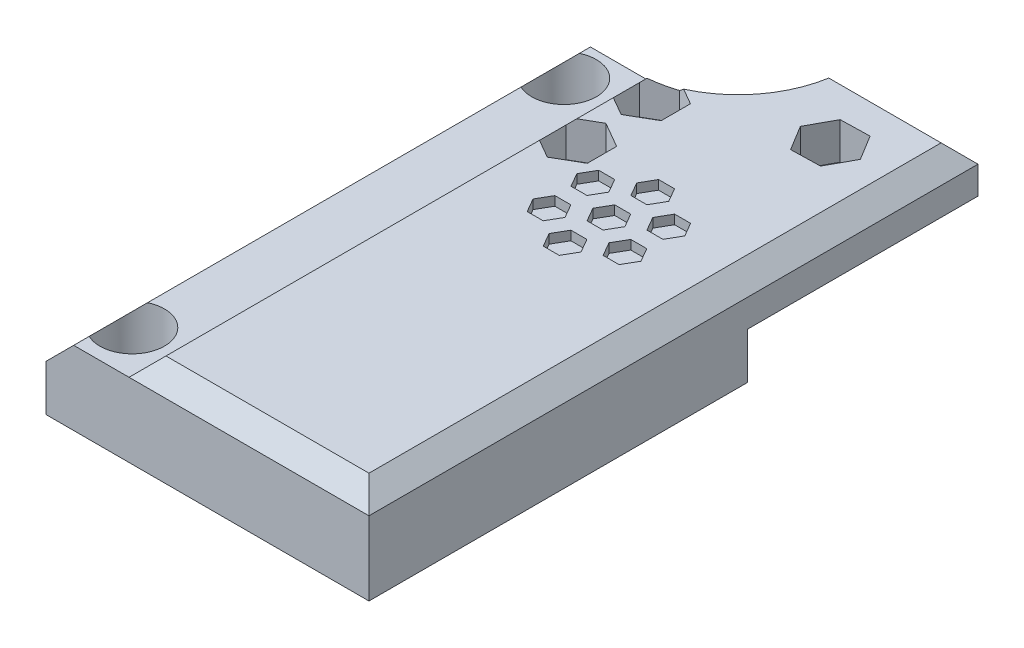
SolidWorks part; units mm, degrees
ref_plane "Front Plane" through (0, 0, 0) normal (0, 0, 1) x (1, 0, 0)
ref_plane "Top Plane" through (0, 0, 0) normal (0, 1, 0) x (1, 0, 0)
ref_plane "Right Plane" through (0, 0, 0) normal (1, 0, 0) x (0, 0, -1)
sketch "Sketch1" plane through (0, 0, 0) normal (0, 1, 0) x (1, 0, 0)
  line L1 (0, 0) -> (26, 0)
  line L2 (0, 0) -> (0, 41)
  line L3 (0, 41) -> (26, 41)
  line L4 (26, 0) -> (26, 41)
  dimension "D1" = 41
  dimension "D2" = 26
extrude "Boss-Extrude1" add sketch "Sketch1" along normal blind 10
sketch "Sketch2" plane through (0, 0, -41) normal (0, 0, -1) x (-1, 0, 0)
  line L0 (-26, 10) -> (-26, 0) construction
  line L1 (-26, 5) -> (0, 5)
  line L2 (-26, 5) -> (-26, 10)
  line L3 (-26, 10) -> (0, 10)
  line L4 (0, 5) -> (0, 10)
extrude "Boss-Extrude2" add sketch "Sketch2" along normal blind 25
sketch "Sketch3" plane through (0, 10, 0) normal (0, 1, 0) x (1, 0, 0)
  line L0 (0, 66) -> (0, 0) construction
  line L1 (0, 66) -> (26, 66) construction
  line L2 (0, 56) -> (0, 66)
  line L3 (0, 66) -> (10, 66)
  arc A0 (0, 56) -> (10, 66) centre (0, 66) ccw
  dimension "D1" = 10
extrude "Cut-Extrude1" cut sketch "Sketch3" against normal up to next
chamfer "Chamfer1" distance 2 angle 45 5 edges at (18, 10, -66) (7.0711, 10, -58.9289) (0, 10, -28) (26, 10, -33) (13, 10, 0)
sketch "Sketch4" plane through (0, 0, 0) normal (-1, 0, 0) x (0, 0, 1)
  line L1 (-56, 8) -> (0, 8)
  line L2 (-56, 8) -> (-56, 0)
  line L3 (-56, 0) -> (0, 0)
  line L4 (0, 8) -> (0, 0)
extrude "Boss-Extrude3" add sketch "Sketch4" along normal blind 9
sketch "Sketch5" plane through (0, 8, 0) normal (0, 1, 0) x (1, 0, 0)
  line L0 (-4.5, 51.6375) -> (-4.5, 4.8375) construction
  line L1 (-9, 0) -> (-9, 56) construction
  circle A0 centre (-4.5, 51.6375) radius 2.15
  circle A1 centre (-4.5, 4.8375) radius 2.15
  dimension "D1" = 4.3
  dimension "D2" = 4.5
  dimension "D3" = 46.8
extrude "Cut-Extrude2" cut sketch "Sketch5" against normal up to next
sketch "Sketch6" plane through (0, 8, 0) normal (0, 1, 0) x (1, 0, 0)
  circle A0 centre (-4.5, 51.6375) radius 3.5
  circle A1 centre (-4.5, 4.8375) radius 3.5
  dimension "D1" = 7
extrude "Cut-Extrude3" cut sketch "Sketch6" against normal blind 5
chamfer "Chamfer3" distance 3 angle 45 1 edges at (-9, 8, -28)
sketch "Sketch10" plane through (0, 10, 0) normal (0, 1, 0) x (1, 0, 0)
  line L0 (24, 2) -> (24, 64) construction
  line L1 (14.7321, 39) -> (13.866, 40.5)
  line L2 (13.866, 40.5) -> (12.134, 40.5)
  line L3 (12.134, 40.5) -> (11.2679, 39)
  line L4 (11.2679, 39) -> (12.134, 37.5)
  line L5 (12.134, 37.5) -> (13.866, 37.5)
  line L6 (13.866, 37.5) -> (14.7321, 39)
  line L7 (14.7321, 43.75) -> (13.866, 45.25)
  line L8 (13.866, 45.25) -> (12.134, 45.25)
  line L9 (12.134, 45.25) -> (11.2679, 43.75)
  line L10 (11.2679, 43.75) -> (12.134, 42.25)
  line L11 (12.134, 42.25) -> (13.866, 42.25)
  line L12 (13.866, 42.25) -> (14.7321, 43.75)
  line L13 (0, 0) -> (13, 39) construction
  line L14 (13, 39) -> (13, 0) construction
  line L16 (13, 0) -> (0, 0) construction
  line L17 (0, 0) -> (13, 0) construction
  line L19 (2, 2) -> (24, 2) construction
  line L20 (17.9796, 39.875) -> (18.8457, 41.375)
  line L21 (18.8457, 41.375) -> (17.9796, 42.875)
  line L22 (17.9796, 42.875) -> (16.2476, 42.875)
  line L23 (16.2476, 42.875) -> (15.3816, 41.375)
  line L24 (15.3816, 41.375) -> (16.2476, 39.875)
  line L25 (16.2476, 39.875) -> (17.9796, 39.875)
  line L26 (16.2476, 35.125) -> (17.9796, 35.125)
  line L27 (17.9796, 35.125) -> (18.8457, 36.625)
  line L28 (18.8457, 36.625) -> (17.9796, 38.125)
  line L29 (17.9796, 38.125) -> (16.2476, 38.125)
  line L30 (16.2476, 38.125) -> (15.3816, 36.625)
  line L31 (15.3816, 36.625) -> (16.2476, 35.125)
  line L32 (11.2679, 34.25) -> (12.134, 32.75)
  line L33 (12.134, 32.75) -> (13.866, 32.75)
  line L34 (13.866, 32.75) -> (14.7321, 34.25)
  line L35 (14.7321, 34.25) -> (13.866, 35.75)
  line L36 (13.866, 35.75) -> (12.134, 35.75)
  line L37 (12.134, 35.75) -> (11.2679, 34.25)
  line L38 (8.0204, 38.125) -> (7.1543, 36.625)
  line L39 (7.1543, 36.625) -> (8.0204, 35.125)
  line L40 (8.0204, 35.125) -> (9.7524, 35.125)
  line L41 (9.7524, 35.125) -> (10.6184, 36.625)
  line L42 (10.6184, 36.625) -> (9.7524, 38.125)
  line L43 (9.7524, 38.125) -> (8.0204, 38.125)
  line L44 (9.7524, 42.875) -> (8.0204, 42.875)
  line L45 (8.0204, 42.875) -> (7.1543, 41.375)
  line L46 (7.1543, 41.375) -> (8.0204, 39.875)
  line L47 (8.0204, 39.875) -> (9.7524, 39.875)
  line L48 (9.7524, 39.875) -> (10.6184, 41.375)
  line L49 (10.6184, 41.375) -> (9.7524, 42.875)
  circle A0 centre (13, 39) radius 1.5 construction
  circle A1 centre (13, 43.75) radius 1.5 construction
  point P55 (13, 39)
  dimension "D1" = 3
  dimension "D2" = 4.75
  dimension "D3" = 11
  dimension "D4" = 13
  dimension "D5" = 37
  dimension "D6" = 6
extrude "Cut-Extrude5" cut sketch "Sketch10" against normal blind 1
sketch "Sketch11" plane through (0, 10, 0) normal (0, 1, 0) x (1, 0, 0)
  line L0 (18, 66) -> (18, 0) construction
  line L1 (6.75, 46.0877) -> (4, 47.6754)
  line L2 (4, 47.6754) -> (1.25, 46.0877)
  line L3 (1.25, 46.0877) -> (1.25, 42.9123)
  line L4 (1.25, 42.9123) -> (4, 41.3246)
  line L5 (4, 41.3246) -> (6.75, 42.9123)
  line L6 (6.75, 42.9123) -> (6.75, 46.0877)
  line L7 (6.75, 54.0877) -> (4, 55.6754)
  line L8 (4, 55.6754) -> (1.25, 54.0877)
  line L9 (1.25, 54.0877) -> (1.25, 50.9123)
  line L10 (1.25, 50.9123) -> (4, 49.3246)
  line L11 (4, 49.3246) -> (6.75, 50.9123)
  line L12 (6.75, 50.9123) -> (6.75, 54.0877)
  line L13 (21.1745, 58.0763) -> (19.5211, 60.7874)
  line L14 (19.5211, 60.7874) -> (16.3466, 60.711)
  line L15 (16.3466, 60.711) -> (14.8255, 57.9237)
  line L16 (14.8255, 57.9237) -> (16.4789, 55.2126)
  line L17 (16.4789, 55.2126) -> (19.6534, 55.289)
  line L18 (19.6534, 55.289) -> (21.1745, 58.0763)
  line L19 (10, 66) -> (26, 66) construction
  line L20 (26, 0) -> (0, 0) construction
  line L21 (4, 52.5) -> (4, 44.5) construction
  line L22 (0, 0) -> (0, 56) construction
  line L25 (2, 54.1678) -> (2, 2) construction
  circle A0 centre (4, 44.5) radius 2.75 construction
  circle A1 centre (4, 52.5) radius 2.75 construction
  circle A2 centre (18, 58) radius 2.75 construction
  dimension "D1" = 5.5
  dimension "D2" = 4
  dimension "D3" = 8
  dimension "D4" = 3.5
  dimension "D5" = 17
extrude "Cut-Extrude6" cut sketch "Sketch11" against normal blind 4
sketch "Sketch12" plane through (0, 10, 0) normal (0, 1, 0) x (1, 0, 0)
  line L0 (4, 55.6754) -> (4, 49.3246) construction
  line L2 (4, 47.6754) -> (4, 41.3246) construction
  line L4 (19.6534, 55.289) -> (16.3466, 60.711) construction
  circle A0 centre (4, 52.5) radius 1.65
  circle A1 centre (4, 44.5) radius 1.65
  circle A2 centre (18, 58) radius 1.65
  dimension "D1" = 3.3
extrude "Cut-Extrude7" cut sketch "Sketch12" against normal up to next
sketch "Sketch14" plane through (0, 0, 0) normal (0, -1, 0) x (1, 0, 0)
  line L0 (26, 0) -> (26, -41) construction
  line L1 (12.75, -17) -> (24.75, -17)
  line L2 (12.75, -17) -> (12.75, -29)
  line L3 (12.75, -29) -> (24.75, -29)
  line L4 (24.75, -17) -> (24.75, -29)
  line L5 (-9, 0) -> (26, 0) construction
  dimension "D1" = 1.25
  dimension "D2" = 17
  dimension "D3" = 12
  dimension "D4" = 12
extrude "Cut-Extrude9" cut sketch "Sketch14" against normal blind 7
